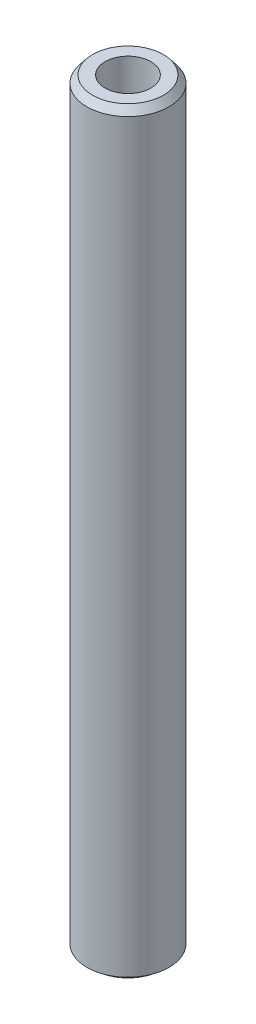
SolidWorks part; units mm, degrees
ref_plane "Front Plane" through (0, 0, 0) normal (0, 0, 1) x (1, 0, 0)
ref_plane "Top Plane" through (0, 0, 0) normal (0, 1, 0) x (1, 0, 0)
ref_plane "Right Plane" through (0, 0, 0) normal (1, 0, 0) x (0, 0, -1)
sketch "Sketch1" plane through (0, 0, 0) normal (0, 1, 0) x (1, 0, 0)
  circle A0 centre (0, 0) radius 32.5
  dimension "SHAFT_OD" = 65
extrude "Boss-Extrude1" add sketch "Sketch1" along normal blind 600
sketch "Sketch2" plane through (0, 0, 0) normal (0, 1, 0) x (1, 0, 0)
  circle A0 centre (0, 0) radius 18.1436
  dimension "BORE_D" = 36.2872
extrude "Cut-Extrude1" cut sketch "Sketch2" along normal through all
chamfer "Chamfer1" distance 5.6537 angle 38.657 2 edges at (0, 600, 32.5) (0, 0, 32.5) first distance on face at (0, 600, 32.5) first distance on face at (0, 0, 18.1436)
